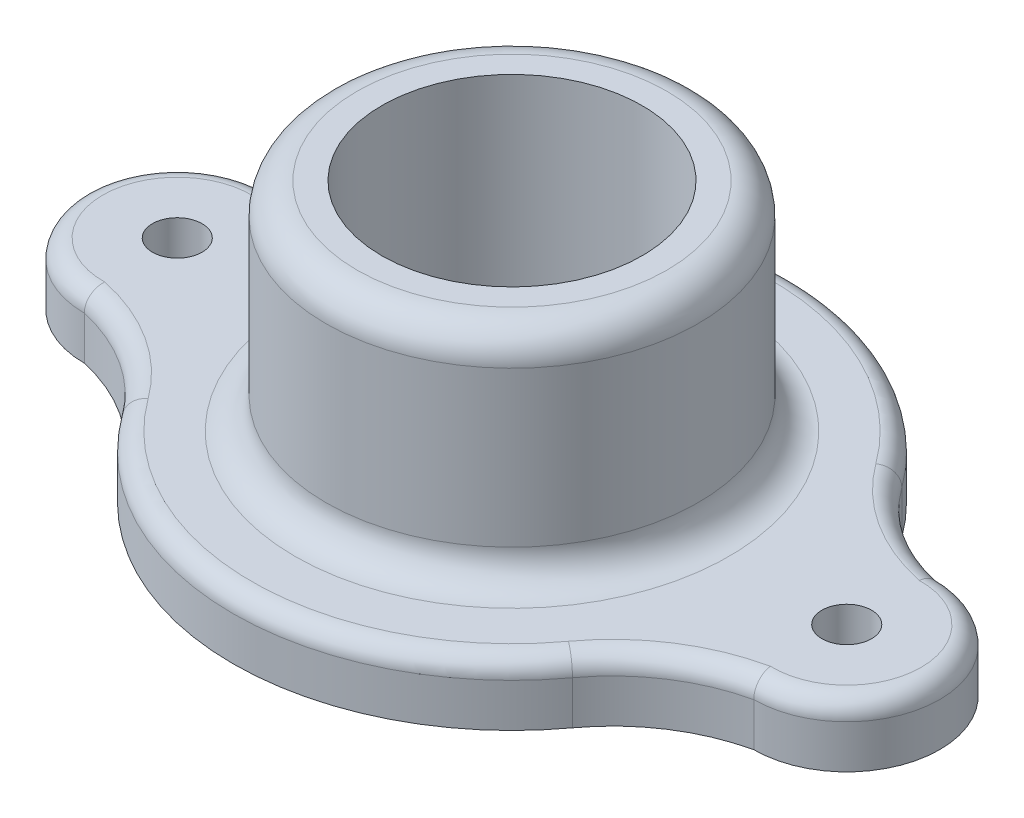
SolidWorks part; units mm, degrees
note: The reader was unsure of these and kept them because the rebuilt part matched: shared geometry of "Sketch5<3>".
ref_plane "Front Plane" through (0, 0, 0) normal (0, 0, 1) x (1, 0, 0)
ref_plane "Top Plane" through (0, 0, 0) normal (0, 1, 0) x (1, 0, 0)
ref_plane "Right Plane" through (0, 0, 0) normal (1, 0, 0) x (0, 0, -1)
sketch "Sketch4" plane through (0, 0, 0) normal (0, 1, 0) x (1, 0, 0)
  line L0 (0, 0) -> (0, 15) construction
  line L1 (0, 0) -> (-12.5525, 0) construction
  arc A0 (36.32, 26.568) -> (-36.32, 26.568) centre (0, 0) ccw
  arc A2 (54, -15) -> (54, 15) centre (54, 0) ccw
  arc A3 (-54, 15) -> (-54, -15) centre (-54, 0) ccw
  arc A5 (-54, 15) -> (-36.32, 26.568) centre (-60.5333, 44.2799) ccw
  arc A6 (-54, -15) -> (-36.32, -26.568) centre (-60.5333, -44.2799) cw
  arc A7 (54, -15) -> (36.32, -26.568) centre (60.5333, -44.2799) ccw
  arc A8 (54, 15) -> (36.32, 26.568) centre (60.5333, 44.2799) cw
  arc A9 (-36.32, -26.568) -> (36.32, -26.568) centre (0, 0) ccw
  circle A10 centre (-54, 0) radius 4
  circle A11 centre (54, 0) radius 4
  dimension "D1" = 30
  dimension "D2" = 90
  dimension "D3" = 30
  dimension "D4" = 8
  dimension "08" = 108
extrude "Boss-Extrude2" add sketch "Sketch4" along normal blind 10
sketch "Sketch5" plane through (0, 10, 0) normal (0, 1, 0) x (1, 0, 0)
  circle A0 centre (0, 0) radius 30
  circle A1 centre (0, 0) radius 21
  dimension "D1" = 60
  dimension "D2" = 42
extrude "Boss-Extrude3" add sketch "Sketch5" along normal blind 35 contours A0 A1 | A1
extrude "Cut-Extrude2" cut sketch "Sketch5<3>" against normal through all contours A1
sketch "Sketch5<3>" plane through (0, 10, 0) normal (0, 1, 0) x (1, 0, 0) same geometry as "Sketch5"
fillet "Fillet3" radius 5 3 edges at (0, 0, 21) (0, 45, 30) (0, 10, 30)
fillet "Fillet4" radius 3 8 edges at (44.1079, 10, 19.176) (69, 10, 0) (44.1079, 10, -19.176) (0, 10, -45) (-44.1079, 10, -19.176) (-44.1079, 10, 19.176) (-69, 10, 0) (0, 10, 45)
